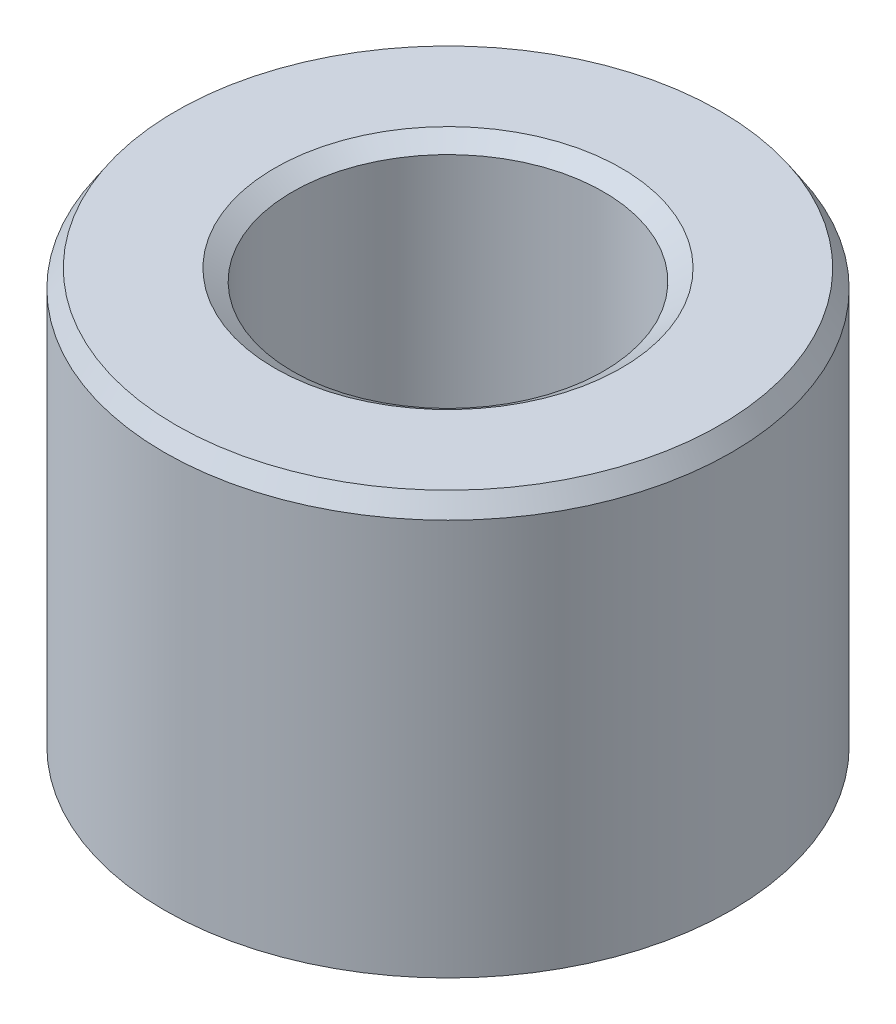
SolidWorks part; units mm, degrees
ref_plane "Front Plane" through (0, 0, 0) normal (0, 0, 1) x (1, 0, 0)
ref_plane "Top Plane" through (0, 0, 0) normal (0, 1, 0) x (1, 0, 0)
ref_plane "Right Plane" through (0, 0, 0) normal (1, 0, 0) x (0, 0, -1)
sketch "Sketch1" plane through (0, 0, 0) normal (0, 1, 0) x (1, 0, 0)
  circle A0 centre (0, 0) radius 42.5
  dimension "SLEEVE_OD" = 85
extrude "Boss-Extrude1" add sketch "Sketch1" along normal blind 63.7994
sketch "Sketch2" plane through (0, 0, 0) normal (0, 1, 0) x (1, 0, 0)
  circle A0 centre (0, 0) radius 23.2961
  dimension "BORE_D" = 46.5922
extrude "Cut-Extrude1" cut sketch "Sketch2" along normal through all
chamfer "Chamfer1" distance 2.6677 angle 33.156 4 edges at (0, 63.7994, 23.2961) (0, 0, 23.2961) (0, 0, 42.5) (0, 63.7994, 42.5) first distance on face at (0, 63.7994, 23.2961) first distance on face at (0, 0, 23.2961) first distance on face at (0, 63.7994, 42.5)
